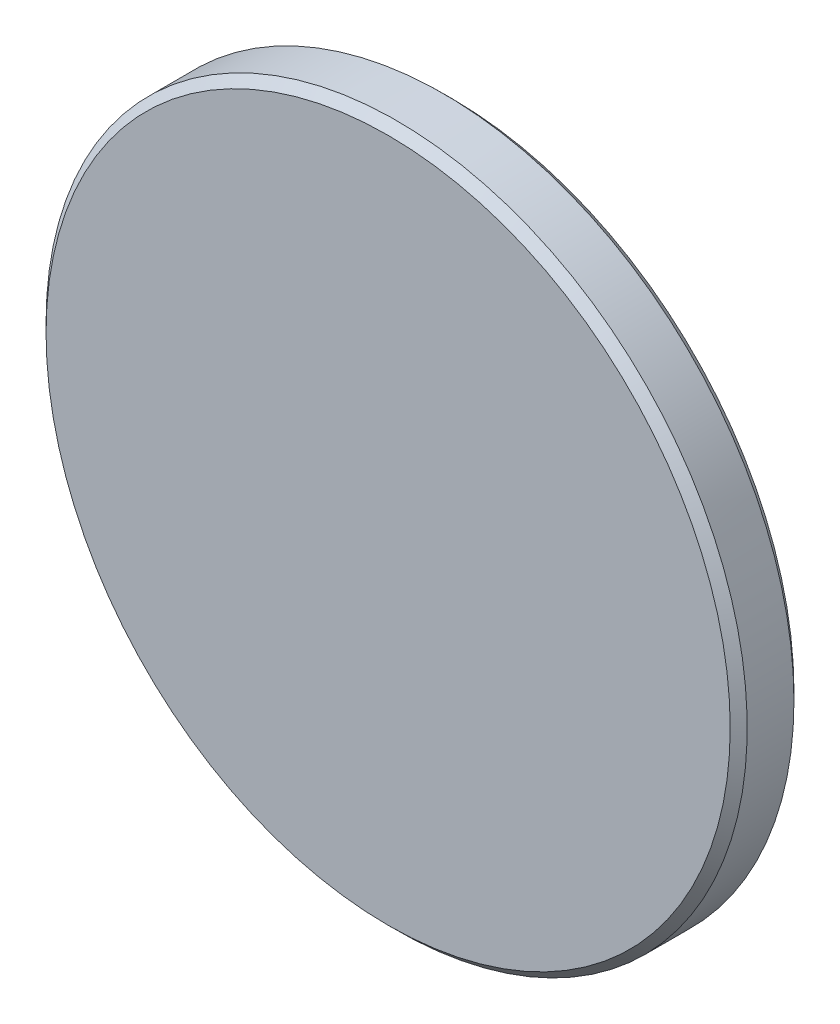
SolidWorks part; units mm, degrees
ref_plane "Front Plane" through (0, 0, 0) normal (0, 0, 1) x (1, 0, 0)
ref_plane "Top Plane" through (0, 0, 0) normal (0, 1, 0) x (1, 0, 0)
ref_plane "Right Plane" through (0, 0, 0) normal (1, 0, 0) x (0, 0, -1)
sketch "Sketch1" plane through (0, 0, 0) normal (0, 0, 1) x (1, 0, 0)
  circle A0 centre (0, 0) radius 20.955
  dimension "D1" = 41.91
extrude "Boss-Extrude1" add sketch "Sketch1" along normal blind 3.81
sketch "Sketch2" plane through (0, 0, 0) normal (1, 0, 0) x (0, 0, -1)
  line L0 (0, 10.824) -> (6.35, 0.029)
  line L1 (6.35, 0.029) -> (0, -10.766)
  line L2 (0, -10.766) -> (0, 10.824)
  dimension "D1" = 21.59
  dimension "D2" = 6.35
extrude "Boss-Extrude2" add sketch "Sketch2" along normal mid plane 3.81
sketch "Sketch3" plane through (-1.905, 0, 0) normal (-1, 0, 0) x (0, 0, 1)
  circle A0 centre (-2.794, 0) radius 1.27
  point P2 (-3.3746, 0)
  dimension "D1" = 2.54
  dimension "D2" = 3.556
extrude "Cut-Extrude1" cut sketch "Sketch3" against normal blind 3.81
fillet "Fillet1" radius 1.27 9 edges at (-1.905, 0.029, 0) (1.905, 0.029, 0) (-1.905, 5.4265, -3.175) (-1.905, -5.3685, -3.175) (1.905, -5.3685, -3.175) (1.905, 5.4265, -3.175) (0, 10.824, 0) (0, -10.766, 0) (0, 0.029, -6.35)
fillet "Chamfer2" radius 0.508 2 edges at (20.955, 0, 3.81) (20.955, 0, 0) profile chamfer
